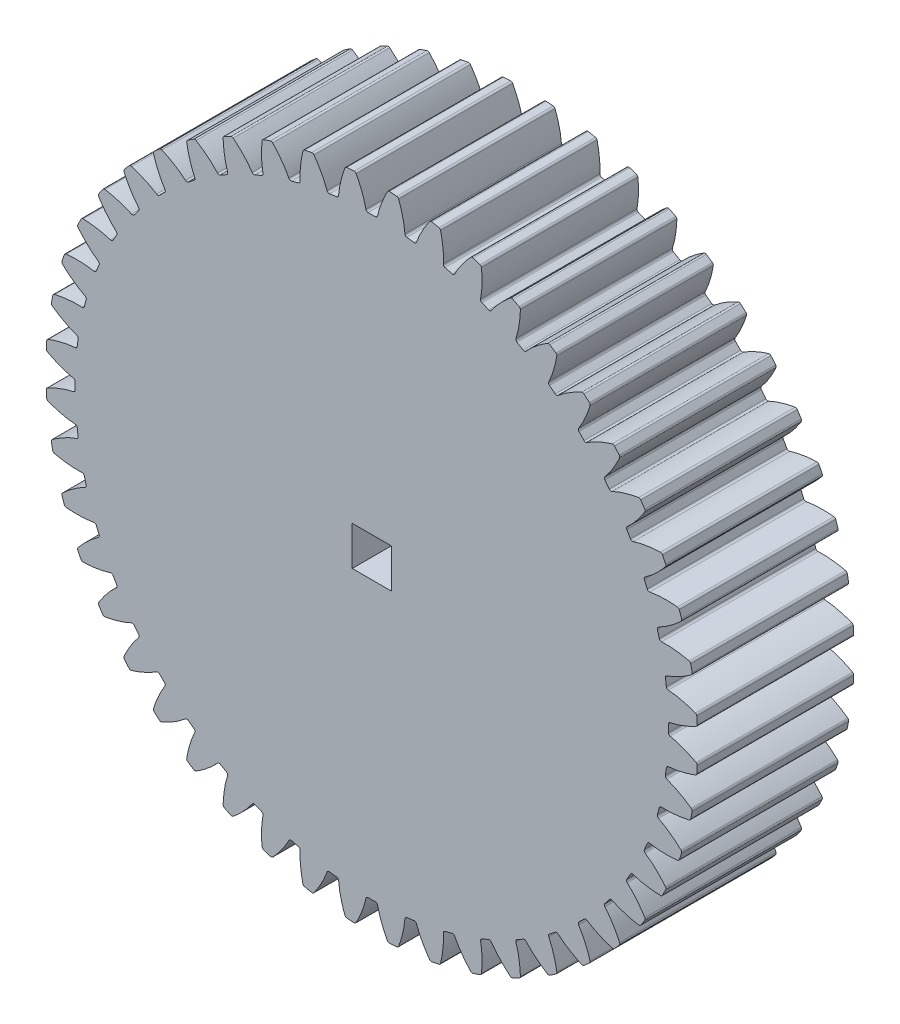
SolidWorks part; units mm, degrees
material "ABS"
ref_plane "Front" through (0, 0, 0) normal (0, 0, 1) x (1, 0, 0)
ref_plane "Top" through (0, 0, 0) normal (0, 1, 0) x (1, 0, 0)
ref_plane "Right" through (0, 0, 0) normal (1, 0, 0) x (0, 0, -1)
sketch "Sketch1" plane through (0, 0, 0) normal (0, 0, 1) x (1, 0, 0)
  circle A0 centre (0, 0) radius 26.4583
  dimension "OutsideDiameter" = 52.9167
extrude "Boss-Extrude1" add sketch "Sketch1" along normal blind 12.7
sketch "Sketch3" plane through (0, 0, 0) normal (0, 0, 1) x (1, 0, 0)
  line L0 (0, 0) -> (43.7181, 0) construction
  line L2 (0, 0) -> (-0.429, 24.0733) construction
  line L3 (0, 0) -> (0.429, 24.0733) construction
  line L4 (0.429, 24.0733) -> (0.4253, 23.8644) construction
  line L5 (0, 0) -> (0, 61.276) construction
  line L6 (-0.429, 24.0733) -> (-0.4253, 23.8644) construction
  circle A0 centre (0, 0) radius 26.4583 construction
  circle A1 centre (0, 0) radius 25.4 construction
  circle A2 centre (0, 0) radius 23.8682 construction
  arc A3 (0.429, 24.0733) -> (-0.429, 24.0733) centre (0, 0) ccw construction
  arc A5 (1.3221, 26.4253) -> (-1.3221, 26.4253) centre (0, 0) ccw
  spline S0 degree 4 poles (-0.4253, 23.8644) (-0.4254, 23.8684) (-0.4259, 23.8798) (-0.4272, 23.9011) (-0.4301, 23.936) (-0.4348, 23.9804) (-0.4421, 24.0378) (-0.4523, 24.1054) (-0.4651, 24.1795) (-0.4807, 24.2602) (-0.4979, 24.3406) (-0.5164, 24.4207) (-0.5362, 24.5004) (-0.5617, 24.5969) (-0.5944, 24.7125) (-0.6357, 24.8475) (-0.6863, 25.0003) (-0.7417, 25.1558) (-0.7995, 25.3086) (-0.8616, 25.4627) (-0.9243, 25.6116) (-0.9932, 25.766) (-1.0588, 25.9084) (-1.1365, 26.0675) (-1.2004, 26.1958) (-1.2892, 26.3647) (-1.343, 26.4643) (-1.4076, 26.5808) (-1.437, 26.6324) (-1.4552, 26.6642) knots 0 0 0 0 0 0.005377 0.015084 0.028532 0.04661 0.064855 0.092111 0.119476 0.146842 0.174209 0.201575 0.228941 0.256307 0.307035 0.361767 0.4165 0.471232 0.525964 0.580697 0.635429 0.690161 0.744894 0.799626 0.854358 0.909091 0.954545 1 1 1 1 1 construction
  spline S1 degree 4 poles (-0.4253, 23.8644) (-0.4254, 23.8684) (-0.4259, 23.8798) (-0.4272, 23.9011) (-0.4301, 23.936) (-0.4348, 23.9804) (-0.4421, 24.0378) (-0.4523, 24.1054) (-0.4651, 24.1795) (-0.4807, 24.2602) (-0.4979, 24.3406) (-0.5164, 24.4207) (-0.5362, 24.5004) (-0.5617, 24.5969) (-0.5944, 24.7125) (-0.6357, 24.8475) (-0.6863, 25.0003) (-0.7417, 25.1558) (-0.7995, 25.3086) (-0.8616, 25.4627) (-0.9243, 25.6116) (-0.9932, 25.766) (-1.0588, 25.9084) (-1.1365, 26.0675) (-1.2004, 26.1958) (-1.27, 26.3281) (-1.3044, 26.3924) (-1.3221, 26.4253) knots 0 0 0 0 0 0.005377 0.015084 0.028532 0.04661 0.064855 0.092111 0.119476 0.146842 0.174209 0.201575 0.228941 0.256307 0.307035 0.361767 0.4165 0.471232 0.525964 0.580697 0.635429 0.690161 0.744894 0.799626 0.854358 0.909091 0.909091 0.909091 0.909091 0.909091
  spline S2 degree 4 poles (0.4253, 23.8644) (0.4254, 23.8684) (0.4259, 23.8798) (0.4272, 23.9011) (0.4301, 23.936) (0.4348, 23.9804) (0.4421, 24.0378) (0.4523, 24.1054) (0.4651, 24.1795) (0.4807, 24.2602) (0.4979, 24.3406) (0.5164, 24.4207) (0.5362, 24.5004) (0.5617, 24.5969) (0.5944, 24.7125) (0.6357, 24.8475) (0.6863, 25.0003) (0.7417, 25.1558) (0.7995, 25.3086) (0.8616, 25.4627) (0.9243, 25.6116) (0.9932, 25.766) (1.0588, 25.9084) (1.1365, 26.0675) (1.2004, 26.1958) (1.2892, 26.3647) (1.343, 26.4643) (1.4076, 26.5808) (1.437, 26.6324) (1.4552, 26.6642) knots 0 0 0 0 0 0.005377 0.015084 0.028532 0.04661 0.064855 0.092111 0.119476 0.146842 0.174209 0.201575 0.228941 0.256307 0.307035 0.361767 0.4165 0.471232 0.525964 0.580697 0.635429 0.690161 0.744894 0.799626 0.854358 0.909091 0.954545 1 1 1 1 1 construction
  spline S3 degree 4 poles (0.4253, 23.8644) (0.4254, 23.8684) (0.4259, 23.8798) (0.4272, 23.9011) (0.4301, 23.936) (0.4348, 23.9804) (0.4421, 24.0378) (0.4523, 24.1054) (0.4651, 24.1795) (0.4807, 24.2602) (0.4979, 24.3406) (0.5164, 24.4207) (0.5362, 24.5004) (0.5617, 24.5969) (0.5944, 24.7125) (0.6357, 24.8475) (0.6863, 25.0003) (0.7417, 25.1558) (0.7995, 25.3086) (0.8616, 25.4627) (0.9243, 25.6116) (0.9932, 25.766) (1.0588, 25.9084) (1.1365, 26.0675) (1.2004, 26.1958) (1.27, 26.3281) (1.3044, 26.3924) (1.3221, 26.4253) knots 0 0 0 0 0 0.005377 0.015084 0.028532 0.04661 0.064855 0.092111 0.119476 0.146842 0.174209 0.201575 0.228941 0.256307 0.307035 0.361767 0.4165 0.471232 0.525964 0.580697 0.635429 0.690161 0.744894 0.799626 0.854358 0.909091 0.909091 0.909091 0.909091 0.909091
  point P0 (0, 24.0771)
  dimension "OutsideDiameter" = 52.9167
  dimension "PitchCircle" = 50.8
  dimension "BaseCircle" = 47.7364
  dimension "DedendumCircle" = 48.1542
sketch "DCLTBC" [suppressed] plane through (0, 0, 0) normal (0, 0, 1) x (1, 0, 0)
  line L0 (0, 0) -> (41.04, 0) construction
  line L1 (-0.4786, 4.7258) -> (-0.5479, 5.4102) construction
  line L2 (0.4786, 4.7258) -> (0.5479, 5.4102) construction
  line L3 (-0.4786, 4.7258) -> (-0.5479, 5.4102)
  line L4 (0.4786, 4.7258) -> (0.5479, 5.4102)
  line L5 (0, 0) -> (0, 104.9356) construction
  circle A0 centre (0, 0) radius 7
  circle A1 centre (0, 0) radius 6 construction
  circle A2 centre (0, 0) radius 5.4378 construction
  arc A3 (0.4786, 4.7258) -> (-0.4786, 4.7258) centre (0, 0) ccw construction
  arc A4 (0.4786, 4.7258) -> (-0.4786, 4.7258) centre (0, 0) ccw
  spline S0 degree 4 poles (-994.168, -107.3553) (-12.2, 3.2885) (-0.6588, 4.7874) (-0.4891, 5.1416) (-0.5565, 5.4563) (-0.5637, 5.4847) (-0.5744, 5.521) (-0.5886, 5.5634) (-0.6059, 5.6094) (-0.6266, 5.659) (-0.6489, 5.708) (-0.6726, 5.7563) (-0.6976, 5.8039) (-0.7293, 5.861) (-0.7696, 5.9285) (-0.8198, 6.006) (-0.8803, 6.0922) (-0.9457, 6.1782) (-1.0132, 6.2611) (-1.0849, 6.3428) (-1.1567, 6.4204) (-1.2347, 6.4989) (-1.3084, 6.5702) (-1.3947, 6.6475) (-1.7815, 6.9846) (-3.2646, 8.0433) (17.3538, -8.1004) (-792.2404, 619.045) knots -0.608405 -0.608405 -0.608405 -0.608405 -0.608405 0.005377 0.015084 0.028532 0.04661 0.064855 0.092111 0.119476 0.146842 0.174209 0.201575 0.228941 0.256307 0.307035 0.361767 0.4165 0.471232 0.525964 0.580697 0.635429 0.690161 0.744894 0.799626 0.854358 1.887491 1.887491 1.887491 1.887491 1.887491 only from (-0.5479, 5.4102) to (-1.5983, 6.8151) construction
  spline S1 degree 4 poles (994.168, -107.3553) (12.2, 3.2885) (0.6588, 4.7874) (0.4891, 5.1416) (0.5565, 5.4563) (0.5637, 5.4847) (0.5744, 5.521) (0.5886, 5.5634) (0.6059, 5.6094) (0.6266, 5.659) (0.6489, 5.708) (0.6726, 5.7563) (0.6976, 5.8039) (0.7293, 5.861) (0.7696, 5.9285) (0.8198, 6.006) (0.8803, 6.0922) (0.9457, 6.1782) (1.0132, 6.2611) (1.0849, 6.3428) (1.1567, 6.4204) (1.2347, 6.4989) (1.3084, 6.5702) (1.3947, 6.6475) (1.7815, 6.9846) (3.2646, 8.0433) (-17.3538, -8.1004) (792.2404, 619.045) knots -0.608405 -0.608405 -0.608405 -0.608405 -0.608405 0.005377 0.015084 0.028532 0.04661 0.064855 0.092111 0.119476 0.146842 0.174209 0.201575 0.228941 0.256307 0.307035 0.361767 0.4165 0.471232 0.525964 0.580697 0.635429 0.690161 0.744894 0.799626 0.854358 1.887491 1.887491 1.887491 1.887491 1.887491 only from (0.5479, 5.4102) to (1.5983, 6.8151) construction
  spline S2 degree 4 poles (-0.5479, 5.4102) (-0.5482, 5.4128) (-0.5492, 5.4201) (-0.5517, 5.4339) (-0.5565, 5.4563) (-0.5637, 5.4847) (-0.5744, 5.521) (-0.5886, 5.5634) (-0.6059, 5.6094) (-0.6266, 5.659) (-0.6489, 5.708) (-0.6726, 5.7563) (-0.6976, 5.8039) (-0.7293, 5.861) (-0.7696, 5.9285) (-0.8198, 6.006) (-0.8803, 6.0922) (-0.9457, 6.1782) (-1.0132, 6.2611) (-1.0849, 6.3428) (-1.1567, 6.4204) (-1.2347, 6.4989) (-1.3084, 6.5702) (-1.3947, 6.6475) (-1.4654, 6.7091) (-1.5415, 6.7705) (-1.5789, 6.8001) (-1.5983, 6.8151) knots 0 0 0 0 0 0.005377 0.015084 0.028532 0.04661 0.064855 0.092111 0.119476 0.146842 0.174209 0.201575 0.228941 0.256307 0.307035 0.361767 0.4165 0.471232 0.525964 0.580697 0.635429 0.690161 0.744894 0.799626 0.854358 0.909091 0.909091 0.909091 0.909091 0.909091
  spline S3 degree 4 poles (0.5479, 5.4102) (0.5482, 5.4128) (0.5492, 5.4201) (0.5517, 5.4339) (0.5565, 5.4563) (0.5637, 5.4847) (0.5744, 5.521) (0.5886, 5.5634) (0.6059, 5.6094) (0.6266, 5.659) (0.6489, 5.708) (0.6726, 5.7563) (0.6976, 5.8039) (0.7293, 5.861) (0.7696, 5.9285) (0.8198, 6.006) (0.8803, 6.0922) (0.9457, 6.1782) (1.0132, 6.2611) (1.0849, 6.3428) (1.1567, 6.4204) (1.2347, 6.4989) (1.3084, 6.5702) (1.3947, 6.6475) (1.4654, 6.7091) (1.5415, 6.7705) (1.5789, 6.8001) (1.5983, 6.8151) knots 0 0 0 0 0 0.005377 0.015084 0.028532 0.04661 0.064855 0.092111 0.119476 0.146842 0.174209 0.201575 0.228941 0.256307 0.307035 0.361767 0.4165 0.471232 0.525964 0.580697 0.635429 0.690161 0.744894 0.799626 0.854358 0.909091 0.909091 0.909091 0.909091 0.909091
  dimension "OutsideDiameter" = 52.9167
  dimension "PitchCircle" = 50.8
  dimension "BaseCircle" = 47.7364
extrude "Cut-Extrude-DCLTBC" [suppressed] cut sketch "DCLTBC" along normal through all
fillet "Fillet-Tip-DCLTBC" [suppressed] radius 0.1775
fillet "Fillet-Root-DCLTBC" [suppressed] radius 0.3551
pattern_circular "CirPattern-DCLTBC" [suppressed] count 48 over 360 of bodies 111
sketch "DCGTBC" plane through (0, 0, 0) normal (0, 0, 1) x (1, 0, 0)
  line L0 (0, 0) -> (41.04, 0) construction
  line L1 (-23.9855, 2.0985) -> (0, 0) construction
  line L2 (0, 0) -> (23.9855, 2.0985) construction
  line L3 (0, 0) -> (-16.5124, 0)
  line L5 (0, 0) -> (0, 104.9356) construction
  circle A0 centre (0, 0) radius 26.4583
  circle A1 centre (0, 0) radius 25.4 construction
  circle A2 centre (0, 0) radius 23.8682 construction
  arc A3 (0.429, 24.0733) -> (-0.429, 24.0733) centre (0, 0) ccw construction
  arc A11 (23.9855, 2.0985) -> (-23.9855, 2.0985) centre (0, 0) ccw
  spline S4 degree 4 poles (999.467, -19.4914) (11.8765, 22.2698) (0.5749, 22.9269) (0.3885, 23.4337) (0.4301, 23.936) (0.4348, 23.9804) (0.4421, 24.0378) (0.4523, 24.1054) (0.4651, 24.1795) (0.4807, 24.2602) (0.4979, 24.3406) (0.5164, 24.4207) (0.5362, 24.5004) (0.5617, 24.5969) (0.5944, 24.7125) (0.6357, 24.8475) (0.6863, 25.0003) (0.7417, 25.1558) (0.7995, 25.3086) (0.8616, 25.4627) (0.9243, 25.6116) (0.9932, 25.766) (1.0588, 25.9084) (1.1365, 26.0675) (1.4565, 26.7098) (2.6294, 28.7681) (-11.2848, 2.8605) (477.6167, 905.7076) knots -0.624598 -0.624598 -0.624598 -0.624598 -0.624598 0.005377 0.015084 0.028532 0.04661 0.064855 0.092111 0.119476 0.146842 0.174209 0.201575 0.228941 0.256307 0.307035 0.361767 0.4165 0.471232 0.525964 0.580697 0.635429 0.690161 0.744894 0.799626 0.854358 1.785966 1.785966 1.785966 1.785966 1.785966 only from (0.4253, 23.8644) to (1.3221, 26.4253) construction
  spline S5 degree 4 poles (-999.467, -19.4914) (-11.8765, 22.2698) (-0.5749, 22.9269) (-0.3885, 23.4337) (-0.4301, 23.936) (-0.4348, 23.9804) (-0.4421, 24.0378) (-0.4523, 24.1054) (-0.4651, 24.1795) (-0.4807, 24.2602) (-0.4979, 24.3406) (-0.5164, 24.4207) (-0.5362, 24.5004) (-0.5617, 24.5969) (-0.5944, 24.7125) (-0.6357, 24.8475) (-0.6863, 25.0003) (-0.7417, 25.1558) (-0.7995, 25.3086) (-0.8616, 25.4627) (-0.9243, 25.6116) (-0.9932, 25.766) (-1.0588, 25.9084) (-1.1365, 26.0675) (-1.4565, 26.7098) (-2.6294, 28.7681) (11.2848, 2.8605) (-477.6167, 905.7076) knots -0.624598 -0.624598 -0.624598 -0.624598 -0.624598 0.005377 0.015084 0.028532 0.04661 0.064855 0.092111 0.119476 0.146842 0.174209 0.201575 0.228941 0.256307 0.307035 0.361767 0.4165 0.471232 0.525964 0.580697 0.635429 0.690161 0.744894 0.799626 0.854358 1.785966 1.785966 1.785966 1.785966 1.785966 only from (-0.4253, 23.8644) to (-1.3221, 26.4253) construction
  spline S6 degree 4 poles (0.4253, 23.8644) (0.4254, 23.8684) (0.4259, 23.8798) (0.4272, 23.9011) (0.4301, 23.936) (0.4348, 23.9804) (0.4421, 24.0378) (0.4523, 24.1054) (0.4651, 24.1795) (0.4807, 24.2602) (0.4979, 24.3406) (0.5164, 24.4207) (0.5362, 24.5004) (0.5617, 24.5969) (0.5944, 24.7125) (0.6357, 24.8475) (0.6863, 25.0003) (0.7417, 25.1558) (0.7995, 25.3086) (0.8616, 25.4627) (0.9243, 25.6116) (0.9932, 25.766) (1.0588, 25.9084) (1.1365, 26.0675) (1.2004, 26.1958) (1.27, 26.3281) (1.3044, 26.3924) (1.3221, 26.4253) knots 0 0 0 0 0 0.005377 0.015084 0.028532 0.04661 0.064855 0.092111 0.119476 0.146842 0.174209 0.201575 0.228941 0.256307 0.307035 0.361767 0.4165 0.471232 0.525964 0.580697 0.635429 0.690161 0.744894 0.799626 0.854358 0.909091 0.909091 0.909091 0.909091 0.909091
  spline S7 degree 4 poles (-0.4253, 23.8644) (-0.4254, 23.8684) (-0.4259, 23.8798) (-0.4272, 23.9011) (-0.4301, 23.936) (-0.4348, 23.9804) (-0.4421, 24.0378) (-0.4523, 24.1054) (-0.4651, 24.1795) (-0.4807, 24.2602) (-0.4979, 24.3406) (-0.5164, 24.4207) (-0.5362, 24.5004) (-0.5617, 24.5969) (-0.5944, 24.7125) (-0.6357, 24.8475) (-0.6863, 25.0003) (-0.7417, 25.1558) (-0.7995, 25.3086) (-0.8616, 25.4627) (-0.9243, 25.6116) (-0.9932, 25.766) (-1.0588, 25.9084) (-1.1365, 26.0675) (-1.2004, 26.1958) (-1.27, 26.3281) (-1.3044, 26.3924) (-1.3221, 26.4253) knots 0 0 0 0 0 0.005377 0.015084 0.028532 0.04661 0.064855 0.092111 0.119476 0.146842 0.174209 0.201575 0.228941 0.256307 0.307035 0.361767 0.4165 0.471232 0.525964 0.580697 0.635429 0.690161 0.744894 0.799626 0.854358 0.909091 0.909091 0.909091 0.909091 0.909091
  dimension "D1" = 5
  dimension "D2" = 5
  dimension "OutsideDiameter" = 52.9167
  dimension "PitchCircle" = 50.8
  dimension "BaseCircle" = 47.7364
extrude "Cut-Extrude-DCGTBC" cut sketch "DCGTBC" along normal through all contours A0 A11 region at (0, 25.4781, 0)
fillet "Fillet-Tip-DCGTBC" radius 0.1775 4 edges at (1.3221, 26.4253, 6.35) (-1.3221, 26.4253, 6.35) (0.4476, 24.0729, 6.35) (-0.4476, 24.0729, 6.35)
pattern_circular "CirPattern-DCGTBC" count 48 over 360 about axis through (0, 0, 12.7) along (0, 0, 1) of "Cut-Extrude-DCGTBC", "Fillet-Tip-DCGTBC"
sketch "Sketch4" plane through (0, 0, 12.7) normal (0, 0, 1) x (1, 0, 0)
  line L1 (1.5875, -1.5875) -> (-1.5875, -1.5875)
  line L2 (1.5875, -1.5875) -> (1.5875, 1.5875)
  line L3 (1.5875, 1.5875) -> (-1.5875, 1.5875)
  line L4 (-1.5875, -1.5875) -> (-1.5875, 1.5875)
  line L5 (1.5875, -1.5875) -> (-1.5875, 1.5875) construction
  line L6 (1.5875, 1.5875) -> (-1.5875, -1.5875) construction
  point P0 (0, 0)
  dimension "D1" = 3.175
extrude "Cut-Extrude2" cut sketch "Sketch4" against normal through all
equation "\"DiametralPitch\"= 24'Diametral Pitch"
equation "\"NumTeeth\"= 48'Number of Teeth"
equation "\"PressureAngle\"= 20deg'Pressure Angle"
equation "\"Addendum\"= 1 / \"DiametralPitch\"'Addendum"
equation "\"Dedendum\"= 1.25 / \"DiametralPitch\"'Dedendum"
equation "\"WorkingDepth\"= 2 / \"DiametralPitch\"'Working Depth - here for REF (Not used in building model)"
equation "\"WholeDepth\"= 2.25 / \"DiametralPitch\"'Whole Depth - here for REF (Not used in building model)"
equation "\"Clearance\"= .25 / \"DiametralPitch\"'Clearance"
equation "\"CircularPitch\"= pi / \"DiametralPitch\"'Circular Pitch - here for REF (Not used in building model)"
equation "\"PitchCircle\"= \"NumTeeth\" / \"DiametralPitch\"'Pitch Circle - or - Pitch Diameter"
equation "\"OutsideDiameter\"= ( \"NumTeeth\" + 2 ) / \"DiametralPitch\"'Outside Diameter"
equation "\"Fillet_Root\"= \"Clearance\" * cos ( \"PressureAngle\" ) * tan ( ( 90 + \"PressureAngle\" ) / 2 ) 'Fillet Root"
equation "\"AddendumCircle\"= \"PitchCircle\" + ( 2 * \"Addendum\" )'Addendum Circle - or - Addendum Diameter"
equation "\"DedendumCircle\"= \"PitchCircle\" - ( 2 * \"Dedendum\" )'Dedendum Circle - or - Dedendum Diameter"
equation "\"BaseCircle\"= \"PitchCircle\" * cos ( \"PressureAngle\" )'Base Circle - Base Diameter"
equation "\"PitchAngle\"= 360deg / \"NumTeeth\"'Pitch Angle"
equation "\"Alpha\"= sqr ( \"PitchCircle\" ^ 2 - \"BaseCircle\" ^ 2 ) / \"BaseCircle\" * 180 / PI - \"PressureAngle\"'Alpha - Used for Calculating Beta"
equation "\"Beta\"= ( \"PitchAngle\" / 4 - ( \"Alpha\" - 90 ) )'Beta - Used in definition of the parameters for the parametric equation driven curve"
equation "\"Gamma\"= ( \"PitchAngle\" / 4 - ( \"Alpha\" + 90 ) )'Gamma - Used in definition of the parameters for the parametric equation driven curve"
equation "\"Phi\"= sqr ( ( \"AddendumCircle\" / 2 ) ^ 2 - ( \"BaseCircle\" / 2 ) ^ 2 ) / ( \"BaseCircle\" / 2 )'Phi - Used in definition of the parameters for the parametric equation driven curve"
equation "\"DCGTBC\"= iif ( \"DedendumCircle\" > \"BaseCircle\" , \"unsuppressed\" , \"suppressed\" )'if Dedendum Circle IS GREATER THAN BaseCircle THEN UnsuppressORSuppress FEATURE"
equation "\"DCLTBC\"= iif ( \"DedendumCircle\" - .002 > \"BaseCircle\" , \"suppressed\" , \"unsuppressed\" )'if Dedendum Circle - .002 IS GREATER THAN BaseCircle THEN SuppressORUnsuppress FEATURE"
equation "\"Cut-Extrude-DCGTBC\"= iif ( \"DedendumCircle\" > \"BaseCircle\" , \"unsuppressed\" , \"suppressed\" )'if Dedendum Circle IS GREATER THAN BaseCircle THEN UnsuppressORSuppress FEATURE"
equation "\"Cut-Extrude-DCLTBC\"= iif ( \"DedendumCircle\" - .002 > \"BaseCircle\" , \"suppressed\" , \"unsuppressed\" )'if Dedendum Circle - .002 IS GREATER THAN BaseCircle THEN SuppressORUnsuppress FEATURE"
equation "\"CirPattern-DCGTBC\"= iif ( \"DedendumCircle\" > \"BaseCircle\" , \"unsuppressed\" , \"suppressed\" )'if Dedendum Circle IS GREATER THAN BaseCircle THEN UnsuppressORSuppress FEATURE"
equation "\"CirPattern-DCLTBC\"= iif ( \"DedendumCircle\" - .002 > \"BaseCircle\" , \"suppressed\" , \"unsuppressed\" )'if Dedendum Circle - .002 IS GREATER THAN BaseCircle THEN SuppressORUnsuppress FEATURE"
equation "\"Fillet-Tip-DCGTBC\"= iif ( \"DedendumCircle\" > \"BaseCircle\" , \"unsuppressed\" , \"suppressed\" )'if Dedendum Circle IS GREATER THAN BaseCircle THEN UnsuppressORSuppress FEATURE"
equation "\"Fillet-Tip-DCLTBC\"= iif ( \"DedendumCircle\" - .002 > \"BaseCircle\" , \"suppressed\" , \"unsuppressed\" )'if Dedendum Circle - .002 IS GREATER THAN BaseCircle THEN SuppressORUnsuppress FEATURE"
equation "\"Fillet-Root-DCLTBC\"= iif ( \"DedendumCircle\" - .002 > \"BaseCircle\" , \"suppressed\" , \"unsuppressed\" )'if Dedendum Circle - .002 IS GREATER THAN BaseCircle THEN SuppressORUnsuppress FEATURE"
equation "\"D1@CirPattern-DCGTBC\"= \"NumTeeth\"'Number of Teeth"
equation "\"D1@CirPattern-DCLTBC\"= \"NumTeeth\"'Number of Teeth"
equation "\"D1@Fillet-Tip-DCGTBC\"= \"Fillet_Root\" / 2 'Tip Rad For Large No of Teeth"
equation "\"D1@Fillet-Tip-DCLTBC\"=\"Fillet_Root\" / 2'Tip Rad For Small No of Teeth"
equation "\"D1@Fillet-Root-DCLTBC\"= \"Fillet_Root\"'Fillet Root"
